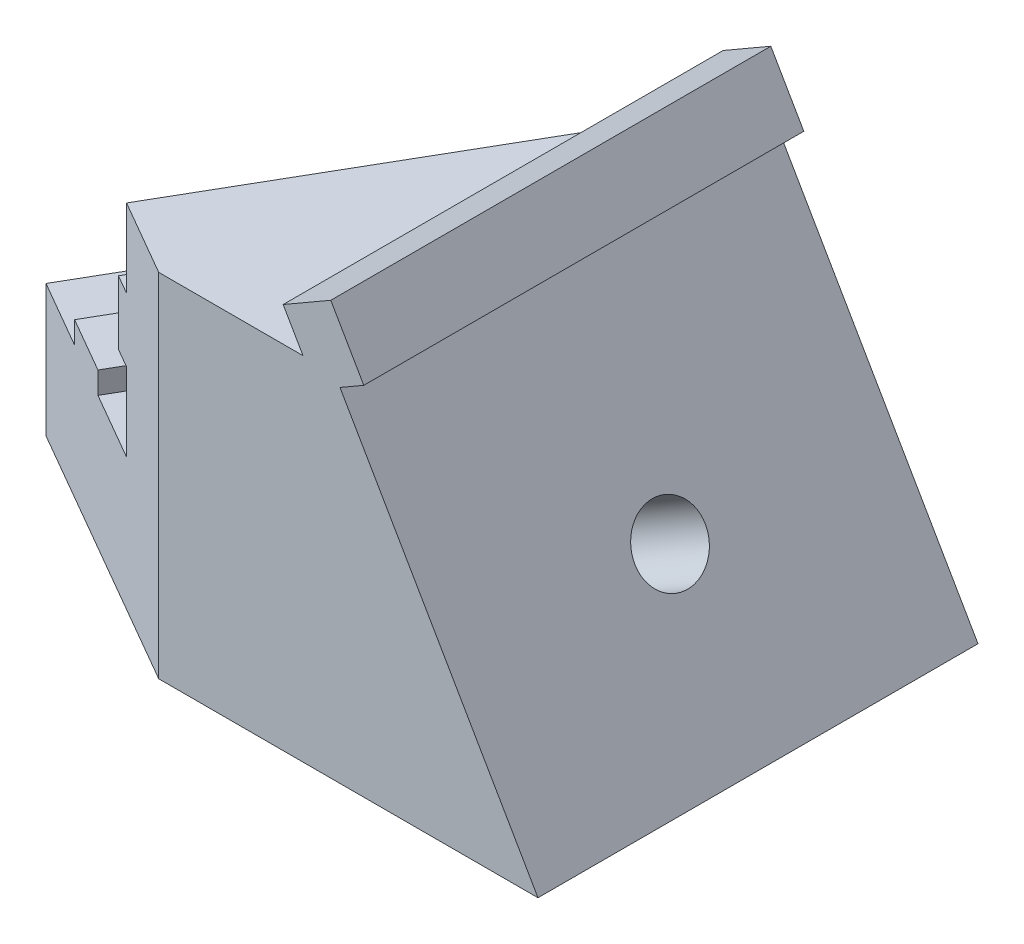
SolidWorks part; units mm, degrees
ref_plane "Front Plane" through (0, 0, 0) normal (0, 0, 1) x (1, 0, 0)
ref_plane "Top Plane" through (0, 0, 0) normal (0, 1, 0) x (1, 0, 0)
ref_plane "Right Plane" through (0, 0, 0) normal (1, 0, 0) x (0, 0, -1)
sketch "Esquisse1" plane through (0, 0, 0) normal (0, 0, 1) x (1, 0, 0)
  line L0 (8, 16) -> (17.2376, 0)
  line L1 (17.2376, 0) -> (0, 0)
  line L2 (0, 0) -> (0, 16)
  line L3 (0, 16) -> (8, 16)
  dimension "D1" = 8
  dimension "D2" = 120
  dimension "D3" = 16
extrude "Boss.-Extru.1" add sketch "Esquisse1" along normal blind 20
sketch "Esquisse2" plane through (12.9282, 7.4641, 0) normal (0.866, 0.5, 0) x (0, 0, -1)
  line L0 (-20, -8.6188) -> (0, -8.6188) construction
  line L3 (-20, -8.6188) -> (-20, 9.8564) construction
  circle A0 centre (-10, -0.6188) radius 1.6
  dimension "D1" = 3.2
  dimension "D2" = 8
  dimension "D3" = 10
extrude "HoleForLauncherFixing" cut sketch "Esquisse2" against normal through all
ref_plane "Plan1" through (8.5981, 4.9641, 0) normal (0.866, 0.5, 0) x (0, 0, -1)
ref_axis "Axe1" through (3.208, 14.3, 0) along (0.5, -0.866, 0)
ref_plane "Plan3" through (0, 0, 0) normal (-0.866, 0, -0.5) x (0, -1, 0)
sketch "Esquisse4" plane through (0, 0, 0) normal (-0.866, 0, -0.5) x (0, -1, 0)
  line L1 (4.4994, 17.8157) -> (-17.7877, 17.8157)
  line L2 (4.4994, 17.8157) -> (4.4994, -17.0003)
  line L3 (4.4994, -17.0003) -> (-17.7877, -17.0003)
  line L4 (-17.7877, 17.8157) -> (-17.7877, -17.0003)
extrude "Enlèv. mat.-Extru.3" cut sketch "Esquisse4" against normal blind 6
ref_plane "Plan4" through (1.7321, 0, -3) normal (-0.5, 0, 0.866) x (0, 1, 0)
ref_plane "Plan5" through (0, 0, 12) normal (0.5, 0, -0.866) x (-0.866, 0, -0.5)
ref_plane "Plan6" through (-8.6603, 0, 15) normal (0.5, 0, -0.866) x (-0.866, 0, -0.5)
sketch "Esquisse5" plane through (-3.4641, 0, 18) normal (0.5, 0, -0.866) x (-0.866, 0, -0.5)
  line L0 (-4, 0) -> (10, 0)
  line L1 (10, 0) -> (10, 6)
  line L2 (10, 6) -> (6.45, 6)
  line L3 (6.45, 6) -> (6.45, 7)
  line L4 (6.45, 7) -> (3.55, 7)
  line L5 (3.55, 7) -> (3.55, 6)
  line L6 (3.55, 6) -> (0, 6)
  line L7 (0, 6) -> (0, 9.55)
  line L8 (0, 9.55) -> (1, 9.55)
  line L9 (1, 9.55) -> (1, 12.45)
  line L10 (1, 12.45) -> (0, 12.45)
  line L11 (0, 12.45) -> (0, 16)
  line L12 (0, 16) -> (-4, 16)
  line L13 (-4, 16) -> (-4, 0)
  dimension "D1" = 10
  dimension "D2" = 2.9
  dimension "D3" = 1
  dimension "D4" = 6
  dimension "D5" = 4
  dimension "D6" = 10
extrude "MakerBeanFixing" add sketch "Esquisse5" along normal blind 21
sketch "Esquisse6" plane through (12.9282, 7.4641, 0) normal (0.866, 0.5, 0) x (0, 0, -1)
  line L0 (0, -8.6188) -> (0, 9.8564) construction
  line L1 (0, 9.3812) -> (-20, 9.3812)
  line L2 (0, 9.3812) -> (0, 12.3812)
  line L3 (0, 12.3812) -> (-20, 12.3812)
  line L4 (-20, 9.3812) -> (-20, 12.3812)
  line L5 (-20, -8.6188) -> (0, -8.6188) construction
  dimension "D1" = 18
  dimension "D2" = 3
extrude "AntiRotationSystem" add sketch "Esquisse6" along normal mid plane 2.5
sketch "Esquisse7" plane through (0, 7, 0) normal (0, 1, 0) x (1, 0, 0)
  line L2 (1.45, 3.4115) -> (3.9615, 1.9615) construction
  line L3 (3.9615, 1.9615) -> (-6.5385, -16.225) construction
  circle A0 centre (0.2058, -1.6436) radius 1.6
  dimension "D1" = 3.2
  dimension "D2" = 5
  dimension "D3" = 1.45
extrude "TopMakerBeanFixingHole" cut sketch "Esquisse7" against normal through all
sketch "Esquisse8" plane through (0, 0, 0) normal (0, 0, -1) x (-1, 0, 0)
  line L0 (-8.2376, 15.5885) -> (-17.2376, 0)
  line L1 (-17.2376, 0) -> (-8.2376, 15.5885) construction
  line L2 (-17.2376, 0) -> (-20.9182, 2.125)
  line L3 (-20.9182, 2.125) -> (-10.4182, 20.3115)
  line L4 (-8.2376, 15.5885) -> (-9.3201, 16.2135)
  line L6 (-17.2376, 0) -> (-8.2376, 15.5885) construction
  line L9 (-9.3201, 16.2135) -> (-7.8201, 18.8115)
  line L10 (-7.8201, 18.8115) -> (-10.4182, 20.3115)
  dimension "D1" = 3
extrude "Enlèv. mat.-Extru.4" cut sketch "Esquisse8" against normal through all
sketch "Esquisse3" plane through (8.5981, 4.9641, 0) normal (0.866, 0.5, 0) x (0, 0, -1)
  circle A0 centre (-10, -0.6188) radius 4.25
  circle A1 centre (-10, -0.6188) radius 1.6 construction
  dimension "D1" = 8.5
extrude "BigHoleForLauncherFixing" cut sketch "Esquisse3" against normal through all
